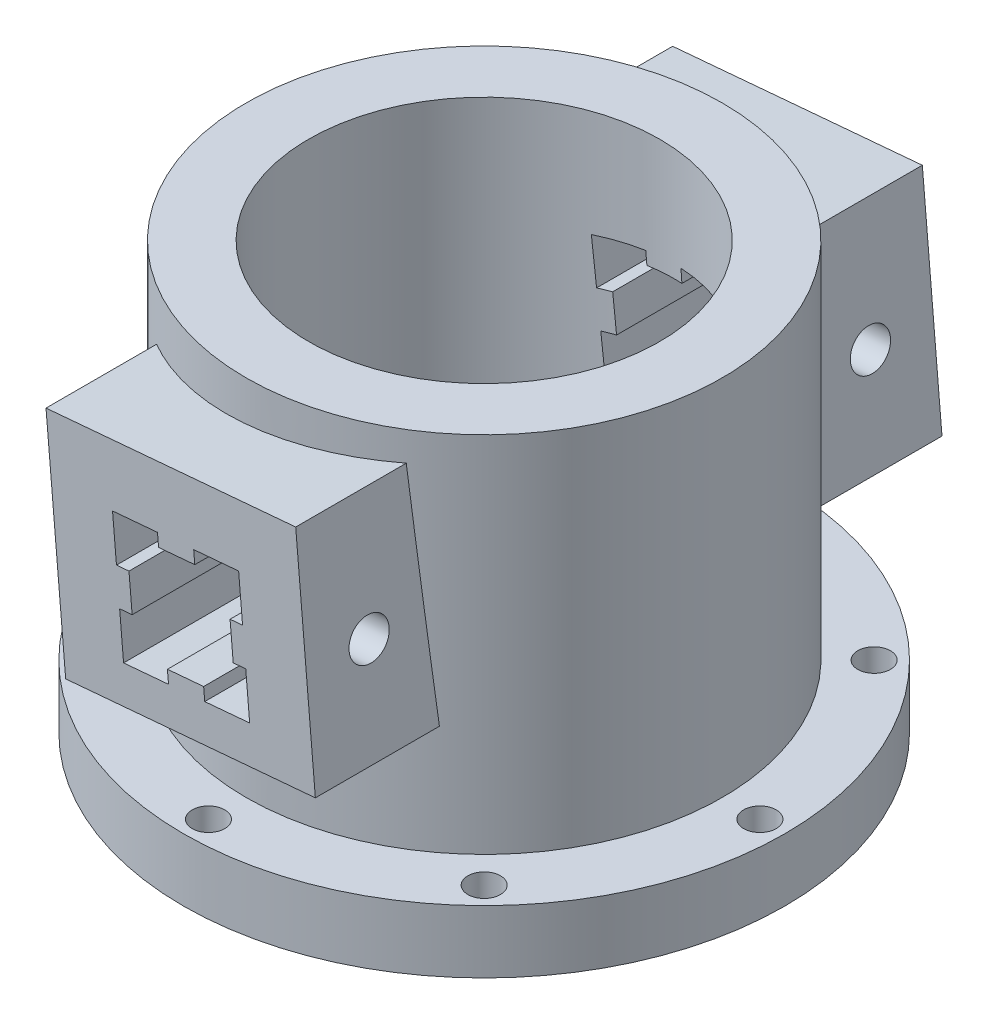
SolidWorks part; units mm, degrees
ref_plane "Front Plane" through (0, 0, 0) normal (0, 0, 1) x (1, 0, 0)
ref_plane "Top Plane" through (0, 0, 0) normal (0, 1, 0) x (1, 0, 0)
ref_plane "Right Plane" through (0, 0, 0) normal (1, 0, 0) x (0, 0, -1)
ref_axis "Axe1" through (0, -1.825, 0) along (0, 1, 0)
sketch "Esquisse1" plane through (0, 0, 0) normal (0, 0, 1) x (1, 0, 0)
  line L0 (14, 0) -> (14, 34)
  line L1 (14, 34) -> (19, 34)
  line L4 (19, 34) -> (19, 5)
  line L5 (19, 5) -> (24, 5)
  line L6 (24, 5) -> (24, 0)
  line L7 (24, 0) -> (14, 0)
  line L8 (0, -1.825) -> (0, 38.325) construction
  dimension "D1" = 14
  dimension "D4" = 5
  dimension "D5" = 24
  dimension "D6" = 5
  dimension "D7" = 34
revolve "Révolution1" add sketch "Esquisse1" angle 360 about axis through (0, -1.825, 0) along (0, 1, 0)
sketch "Esquisse4" plane through (0, 0, 0) normal (0, -1, 0) x (-1, 0, 0)
  circle A0 centre (0, -22) radius 1.3
  dimension "D1" = 2.6
  dimension "D2" = 22
extrude "FixingHole" cut sketch "Esquisse4" against normal through all
pattern_circular "FixingHoleRepetition" count 8 over 360 about axis through (0, -1.825, 0) along (0, 1, 0) of "FixingHole"
ref_plane "Plan1" through (0, 0, 15) normal (0, 0, 1) x (1, 0, 0)
sketch "Esquisse5" plane through (0, 0, 15) normal (0, 0, 1) x (1, 0, 0)
  line L0 (9.9619, 31.6746) -> (11.5308, 13.7431)
  line L1 (11.5308, 13.7431) -> (-8.3931, 12)
  line L2 (-8.3931, 12) -> (-9.9619, 29.9315)
  line L3 (-9.9619, 29.9315) -> (9.9619, 31.6746)
  line L4 (0, -1.825) -> (0, 38.325) construction
  line L5 (5.408, 26.3575) -> (5.7218, 22.7712)
  line L6 (24, 5) -> (-24, 5) construction
  line L27 (5.7218, 22.7712) -> (4.7241, 22.6839)
  line L28 (4.7241, 22.6839) -> (4.9768, 19.7949)
  line L29 (4.9768, 19.7949) -> (5.9745, 19.8822)
  line L30 (5.9745, 19.8822) -> (6.2883, 16.2959)
  line L31 (6.2883, 16.2959) -> (2.702, 15.9822)
  line L32 (2.702, 15.9822) -> (2.6147, 16.9799)
  line L33 (2.6147, 16.9799) -> (-0.2742, 16.7271)
  line L34 (-0.2742, 16.7271) -> (-0.187, 15.7294)
  line L35 (-0.187, 15.7294) -> (-3.7733, 15.4156)
  line L36 (-3.7733, 15.4156) -> (-4.087, 19.0019)
  line L37 (-4.087, 19.0019) -> (-3.0893, 19.0892)
  line L38 (-3.0893, 19.0892) -> (-3.3421, 21.9782)
  line L39 (-3.3421, 21.9782) -> (-4.3398, 21.8909)
  line L40 (-4.3398, 21.8909) -> (-4.6535, 25.4772)
  line L41 (-4.6535, 25.4772) -> (-1.0672, 25.791)
  line L42 (-1.0672, 25.791) -> (-0.9799, 24.7933)
  line L43 (-0.9799, 24.7933) -> (1.909, 25.046)
  line L44 (1.909, 25.046) -> (1.8217, 26.0437)
  line L45 (1.8217, 26.0437) -> (5.408, 26.3575)
  point P6 (0, 30.8031)
  point P7 (6.2073, 23.0328)
  point P8 (-2.2993, 15.6809)
  point P9 (-3.215, 25.7351)
  dimension "D1" = 5
  dimension "D2" = 18
  dimension "D3" = 7
  dimension "D4" = 20
  dimension "D5" = 10.1
  dimension "D6" = 5
  dimension "D7" = 1.0015
  dimension "D10" = 10.1
  dimension "D11" = 3.6
  dimension "D13" = 3
extrude "RightFixing" add sketch "Esquisse5" along normal blind 10
sketch "Esquisse7" plane through (12.6364, 1.1055, 0) normal (0.9962, 0.0872, 0) x (0, 0, -1)
  line L1 (-25, 12.6858) -> (-25, 30.6858) construction
  line L2 (-25, 12.6858) -> (-15.1011, 12.6858) construction
  circle A1 centre (-20, 20.8358) radius 1.6
  dimension "D1" = 3.2
  dimension "D4" = 8.15
  dimension "D5" = 5
extrude "TopFixingHoles" cut sketch "Esquisse7" against normal up to next
mirror "FixingSymetry" about plane through (0, 0, 0) normal (0, 0, 1) of "TopFixingHoles", "RightFixing"
sketch "Esquisse6" plane through (0, 0, 25) normal (0, 0, 1) x (1, 0, 0)
  line L22 (5.408, 26.3575) -> (5.7218, 22.7712)
  line L23 (5.7218, 22.7712) -> (4.7241, 22.6839)
  line L24 (4.7241, 22.6839) -> (4.9768, 19.7949)
  line L25 (4.9768, 19.7949) -> (5.9745, 19.8822)
  line L26 (5.9745, 19.8822) -> (6.2883, 16.2959)
  line L27 (6.2883, 16.2959) -> (2.702, 15.9822)
  line L28 (2.702, 15.9822) -> (2.6147, 16.9799)
  line L29 (2.6147, 16.9799) -> (-0.2742, 16.7271)
  line L30 (-0.2742, 16.7271) -> (-0.187, 15.7294)
  line L31 (-0.187, 15.7294) -> (-3.7733, 15.4156)
  line L32 (-3.7733, 15.4156) -> (-4.087, 19.0019)
  line L33 (-4.087, 19.0019) -> (-3.0893, 19.0892)
  line L34 (-3.0893, 19.0892) -> (-3.3421, 21.9782)
  line L35 (-3.3421, 21.9782) -> (-4.3398, 21.8909)
  line L36 (-4.3398, 21.8909) -> (-4.6535, 25.4772)
  line L37 (-4.6535, 25.4772) -> (-1.0672, 25.791)
  line L38 (-1.0672, 25.791) -> (-0.9799, 24.7933)
  line L39 (-0.9799, 24.7933) -> (1.909, 25.046)
  line L40 (1.909, 25.046) -> (1.8217, 26.0437)
  line L41 (1.8217, 26.0437) -> (5.408, 26.3575)
extrude "HoleForFixing" cut sketch "Esquisse6" against normal through all
